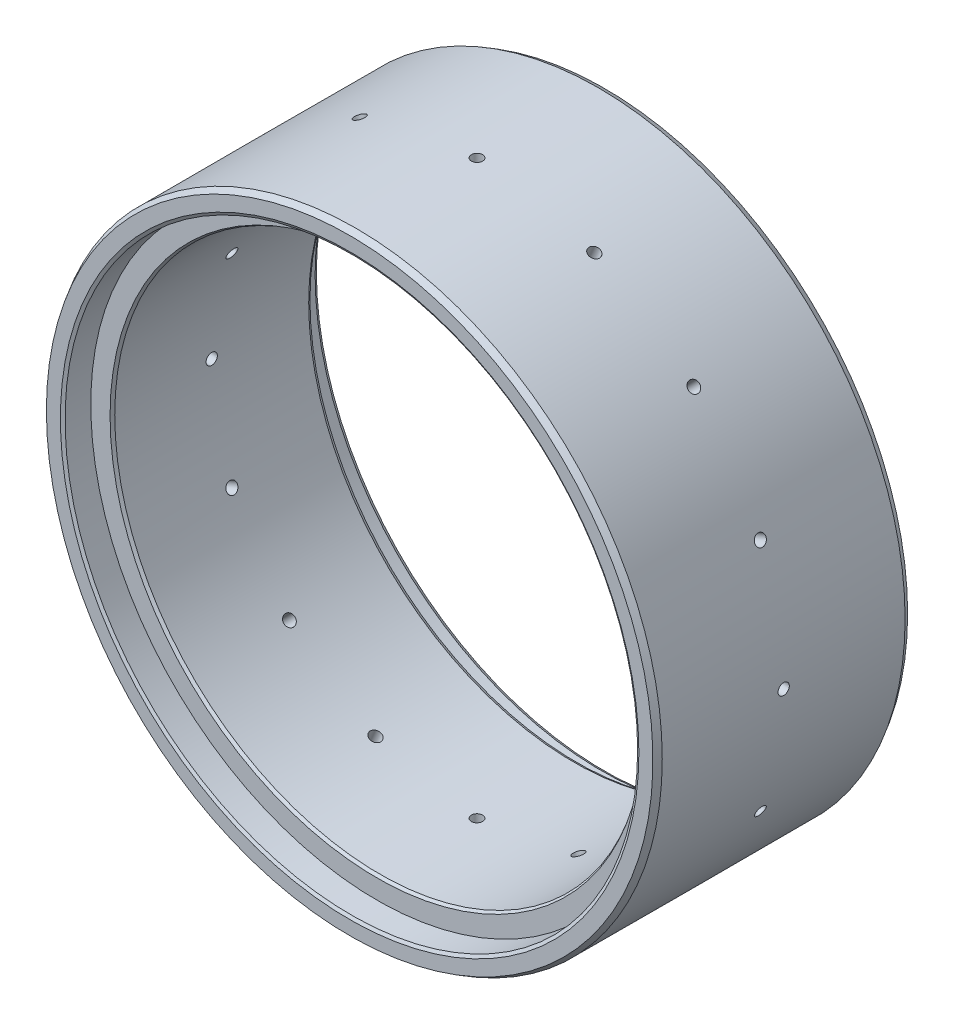
SolidWorks part; units mm, degrees
material "6061-T6 (SS)"
ref_plane "Front Plane" through (0, 0, 0) normal (0, 0, 1) x (1, 0, 0)
ref_plane "Top Plane" through (0, 0, 0) normal (0, 1, 0) x (1, 0, 0)
ref_plane "Right Plane" through (0, 0, 0) normal (1, 0, 0) x (0, 0, -1)
sketch "Sketch1" plane through (0, 0, 0) normal (0, 0, 1) x (1, 0, 0)
  circle A0 centre (0, 0) radius 68.199
  circle A1 centre (0, 0) radius 58.9915
  dimension "D1" = 136.398
  dimension "D2" = 117.983
extrude "Extrude1" add sketch "Sketch1" along normal mid plane 56.642
sketch "Sketch11" plane through (0, 0, -28.321) normal (0, 0, -1) x (-1, 0, 0)
  circle A0 centre (0, 0) radius 63.66
  dimension "D1" = 127.32
extrude "Extrude2" cut sketch "Sketch11" against normal blind 6.096
mirror "Mirror1" about plane through (0, 0, 0) normal (0, 0, 1) of "Extrude2"
sketch "Sketch2" plane through (0, 0, 0) normal (0, 0, 1) x (1, 0, 0)
  line L0 (0, 0) -> (0, 68.199) construction
  line L1 (0, 0) -> (13.305, 66.8886) construction
  circle A0 centre (0, 0) radius 68.199 construction
  dimension "D1" = 11.25
ref_plane "Plane1" through (0, 68.199, 0) normal (0, 1, 0) x (-1, 0, 0)
ref_plane "Plane2" through (13.305, 66.8886, 0) normal (0.1951, 0.9808, 0) x (-0.9808, 0.1951, 0)
sketch "Sketch3" plane through (0, 68.199, 0) normal (0, 1, 0) x (-1, 0, 0)
  line L0 (0, 0) -> (0, 28.321) construction
  line L1 (0, 28.321) -> (0, -28.321) construction
  line L2 (68.199, 28.321) -> (-68.199, 28.321) construction
  point P7 (0, 14.1605)
sketch "Sketch6" plane through (13.305, 66.8886, 0) normal (0.1951, 0.9808, 0) x (-0.9808, 0.1951, 0)
  line L0 (0, 0) -> (0, 28.321) construction
  line L1 (68.199, 28.321) -> (-68.199, 28.321) construction
  point P5 (0, 14.1605)
hole_wizard "Tap Drill for M3x0.5 Tap1" positions "Sketch5" profile "Sketch4" hole size "M3x0.5" standard "Ansi Metric"
sketch "Sketch5" plane through (0, 68.199, 0) normal (0, 1, 0) x (-1, 0, 0)
  point P6 (0, 0)
sketch "Sketch4" plane through (0, 68.199, 0) normal (1, 0, 0) x (0, 0, 1)
  line L0 (0, 0) -> (0, 10.9111)
  line L1 (0, 10.9111) -> (1.25, 10.16)
  line L2 (1.25, 10.16) -> (1.25, 0)
  line L5 (1.25, 0) -> (0, 0)
  line L10 (0, 10.9111) -> (-1.25, 10.16) construction
  line L11 (0, -6.35) -> (0, 107.95) construction
  dimension "Hole Dia." = 2.5
  dimension "Hole Depth" = 10.16
  dimension "Drill Angle" = 118
pattern_circular "CirPattern1" count 16 over 360 about axis through (0, 0, 28.321) along (0, 0, -1) of "Tap Drill for M3x0.5 Tap1"
chamfer "Chamfer1" distance 0.381 angle 60 4 edges at (-58.9915, 0, -22.225) (-63.66, 0, 28.321) (58.9915, 0, 22.225) (-63.66, 0, -28.321) first distance on face at (-58.9915, 0, -22.225) first distance on face at (-63.66, 0, 22.225) first distance on face at (58.9915, 0, 22.225) first distance on face at (-63.66, 0, -28.321)
chamfer "Chamfer3" distance 0.762 angle 60 2 edges at (68.199, 0, 28.321) (68.199, 0, -28.321) first distance on face at (64.3199, 0, 28.321) first distance on face at (64.041, 0, -28.321)
